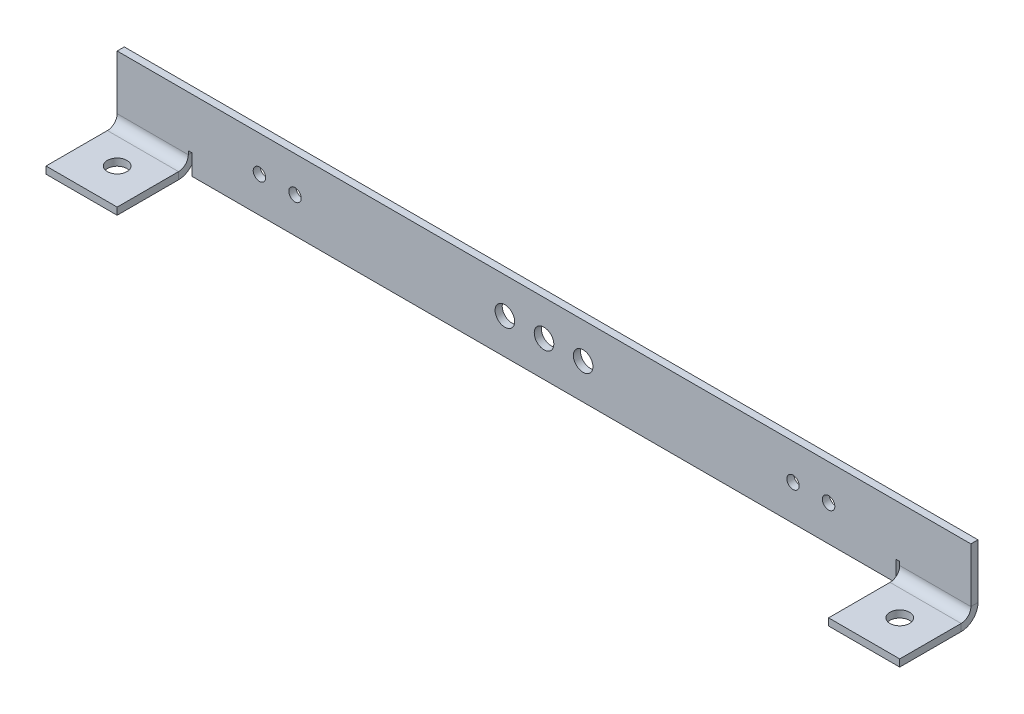
SolidWorks part; units mm, degrees
note: The reader was unsure of these and kept them because the rebuilt part matched: flange length of "边线-法兰1".
ref_plane "前视基准面" through (0, 0, 0) normal (0, 0, 1) x (1, 0, 0)
ref_plane "上视基准面" through (0, 0, 0) normal (0, 1, 0) x (1, 0, 0)
ref_plane "右视基准面" through (0, 0, 0) normal (1, 0, 0) x (0, 0, -1)
sketch "草图1" plane through (0, 0, 0) normal (0, 0, 1) x (1, 0, 0)
  line L0 (0, 0) -> (0, 58.0468) construction
  line L1 (-120, -20) -> (-120, 0)
  line L2 (120, -20) -> (120, 0)
  line L3 (-120, 0) -> (120, 0)
  line L5 (0, 0) -> (120, 0) construction
  line L9 (120, -20) -> (-120, -20)
  point P13 (0, -20)
  dimension "D1" = 20
  dimension "D3" = 120
base flange "基体-法兰1" sketch "草图1" thickness 2 reverse thickness direction no parameters "D1"=2.7366
edge flange "边线-法兰1" sketch "草图8" flange angle 90 flange length 22 flange position material inside bend radius 2.7366 thickness 2 relief rectangular parameters "D6"=10
sketch "草图8" plane through (0, -20, 0) normal (0, 1, 0) x (-1, 0, 0)
  line L2 (100, 0) -> (100, 20)
  line L3 (100, 20) -> (120, 20)
  line L4 (120, 20) -> (120, 0)
  line L10 (120, 0) -> (-120, 0) construction
  line L11 (120, 0) -> (100, 0)
  dimension "D1" = 20
  dimension "D2" = 20
bend "边线折弯1" bend radius 2.7366 bend angle 90 parameters "D5"=1
sketch "草图10" plane through (0, -18, 0) normal (0, 1, 0) x (1, 0, 0)
  line L0 (-120, -20) -> (-100, -20) construction
  line L1 (-100, -20) -> (-100, -2.7366) construction
  circle A0 centre (-110, -10) radius 2.75
  dimension "D3" = 5.5
  dimension "D1" = 10
  dimension "D2" = 10
extrude "切除-拉伸2" cut sketch "草图10" against normal blind 10 normal cut yes
mirror "镜向1" about plane through (0, 0, 0) normal (1, 0, 0) of "切除-拉伸2", "边线-法兰1"
bend "镜向折弯1" bend radius 2.7366 bend angle 90 parameters "D5"=2
sketch "草图11" plane through (0, 0, -2) normal (0, 0, -1) x (-1, 0, 0)
  line L0 (0, -10) -> (0, -20) construction
  line L1 (99, -20) -> (-99, -20) construction
  line L2 (-120, 0) -> (120, 0) construction
  line L3 (-120, -15.2634) -> (-120, 0) construction
  circle A0 centre (0, -10) radius 2.75
  circle A1 centre (-11, -10) radius 2.75
  circle A2 centre (11, -10) radius 2.75
  circle A3 centre (-80, -10) radius 1.75
  circle A4 centre (-70, -10) radius 1.75
  circle A5 centre (80, -10) radius 1.75
  circle A6 centre (70, -10) radius 1.75
  dimension "D1" = 5.5
  dimension "D4" = 3.5
  dimension "D6" = 40
  dimension "D2" = 10
  dimension "D3" = 11
  dimension "D5" = 2
extrude "切除-拉伸3" cut sketch "草图11" against normal blind 10 normal cut yes
sketch "折弯-线1" plane through (0, 0, 0) normal (0, 1, 0) x (1, 0, 0)
sketch "边界框1" plane through (0, 0, 0) normal (0, 1, 0) x (1, 0, 0)
sheet metal parameters "钣金6" thickness 2 parameters "D1"=2.7366
flat pattern "平板型式6" [suppressed]
sketch "折弯-线2" plane through (0, 0, 0) normal (0, 1, 0) x (1, 0, 0)
sketch "边界框2" [suppressed] plane through (0, 0, 0) normal (0, 1, 0) x (1, 0, 0)
sheet metal parameters "钣金7" thickness 2 parameters "D1"=2.7366
flat pattern "平板型式6" [suppressed]
sketch "折弯-线2" plane through (0, 0, 0) normal (0, 1, 0) x (1, 0, 0)
sketch "边界框2" [suppressed] plane through (0, 0, 0) normal (0, 1, 0) x (1, 0, 0)
bend of the flat pattern "展开-<边线折弯1>1"
sheet metal parameters "钣金8" thickness 2 parameters "D1"=2.7366
flat pattern "平板型式6" [suppressed]
sketch "折弯-线2" plane through (0, 0, 0) normal (0, 1, 0) x (1, 0, 0)
sketch "边界框2" [suppressed] plane through (0, 0, 0) normal (0, 1, 0) x (1, 0, 0)
bend of the flat pattern "展开-<边线折弯1>1"
bend of the flat pattern "展开-<镜向折弯1>1"
sheet metal parameters "钣金10" thickness 2 parameters "D1"=2.7366
flat pattern "平板型式6" [suppressed]
sketch "折弯-线2" plane through (0, 0, 0) normal (0, 1, 0) x (1, 0, 0)
sketch "边界框2" [suppressed] plane through (0, 0, 0) normal (0, 1, 0) x (1, 0, 0)
bend of the flat pattern "展开-<边线折弯1>1"
sheet metal parameters "钣金11" thickness 2 parameters "D1"=2.7366
flat pattern "平板型式6" [suppressed]
sketch "折弯-线2" plane through (0, 0, 0) normal (0, 1, 0) x (1, 0, 0)
sketch "边界框2" [suppressed] plane through (0, 0, 0) normal (0, 1, 0) x (1, 0, 0)
bend of the flat pattern "展开-<边线折弯1>1"
bend of the flat pattern "展开-<镜向折弯1>1"
